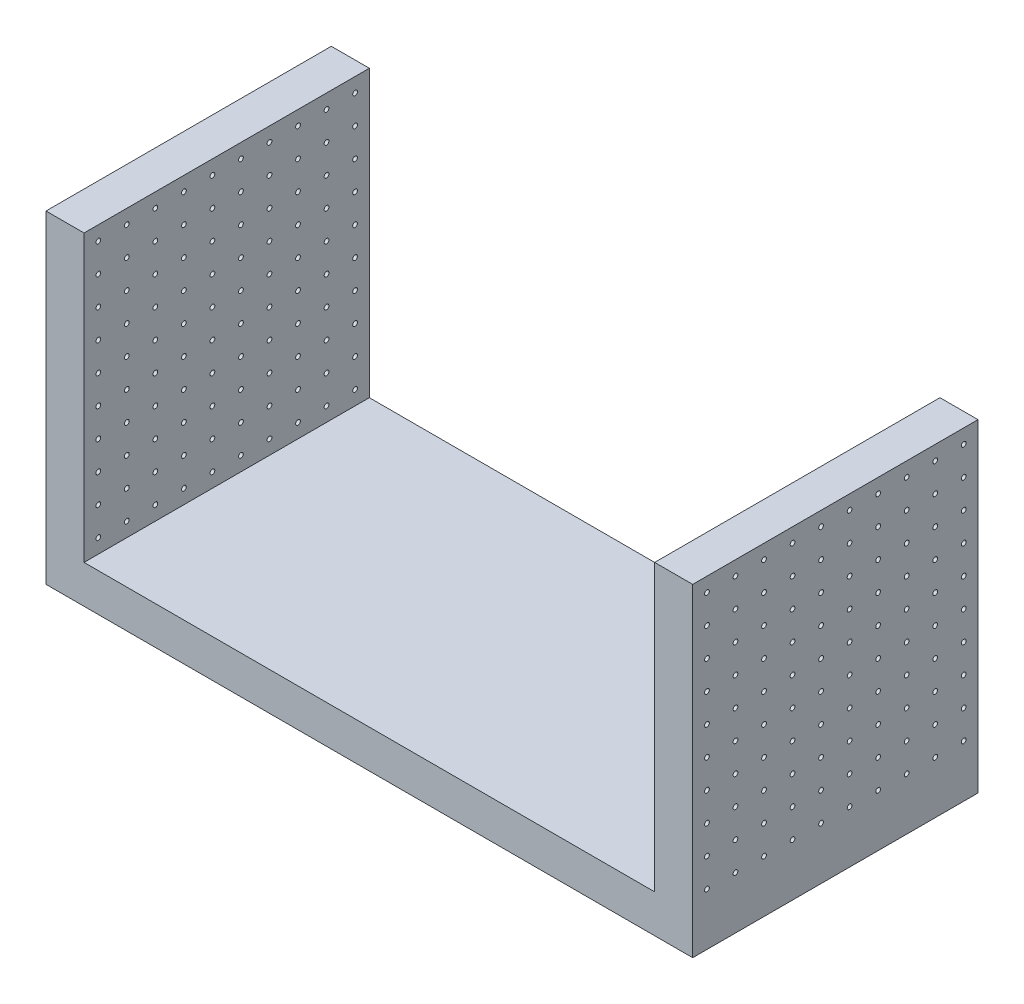
SolidWorks part; units mm, degrees
ref_plane "Front Plane" through (0, 0, 0) normal (0, 0, 1) x (1, 0, 0)
ref_plane "Top Plane" through (0, 0, 0) normal (0, 1, 0) x (1, 0, 0)
ref_plane "Right Plane" through (0, 0, 0) normal (1, 0, 0) x (0, 0, -1)
sketch "Sketch1" plane through (0, 0, 0) normal (0, 0, 1) x (1, 0, 0)
  line L1 (17, -8.5) -> (-17, -8.5)
  line L2 (17, -8.5) -> (17, 8.5)
  line L3 (17, 8.5) -> (-17, 8.5)
  line L4 (-17, -8.5) -> (-17, 8.5)
  line L5 (17, -8.5) -> (-17, 8.5) construction
  line L6 (17, 8.5) -> (-17, -8.5) construction
  point P0 (0, 0)
  dimension "D1" = 34
  dimension "D2" = 17
extrude "Boss-Extrude1" add sketch "Sketch1" along normal blind 7.5 and the other way blind 7.5
sketch "Sketch2" plane through (0, 0, 7.5) normal (0, 0, 1) x (1, 0, 0)
  line L0 (17, 8.5) -> (-17, 8.5) construction
  line L1 (15, -6.5) -> (-15, -6.5)
  line L2 (15, -6.5) -> (15, 8.5)
  line L3 (15, 8.5) -> (-15, 8.5)
  line L4 (-15, -6.5) -> (-15, 8.5)
  line L5 (15, -6.5) -> (-15, 8.5) construction
  line L6 (15, 8.5) -> (-15, -6.5) construction
  line L7 (-17, -8.5) -> (17, -8.5) construction
  line L8 (-17, 8.5) -> (-17, -8.5) construction
  line L9 (0, 1) -> (0, 0) construction
  point P0 (0, 1)
  dimension "D1" = 2
  dimension "D2" = 2
extrude "Cut-Extrude1" cut sketch "Sketch2" against normal up to surface (15 mm away) up to face at (0, 0, -7.5)
sketch "Sketch3" plane through (17, 0, 0) normal (1, 0, 0) x (0, 0, -1)
  line L0 (-6.75, 7.75) -> (-6.75, 8.5) construction
  line L1 (7.5, 8.5) -> (-7.5, 8.5) construction
  line L2 (-6.75, 7.75) -> (-7.5, 7.75) construction
  line L3 (-7.5, -8.5) -> (-7.5, 8.5) construction
  circle A0 centre (-6.75, 7.75) radius 0.125
  dimension "D3" = 0.25
  dimension "D1" = 0.75
  dimension "D2" = 0.75
extrude "Cut-Extrude2" cut sketch "Sketch3" against normal up to surface (34 mm away) up to face at (-17, 0, 0)
pattern_linear "LPattern1" count 10 spacing 1.5 along (0, 0, -1) count 10 spacing 1.5 along (0, -1, 0) of "Cut-Extrude2"
